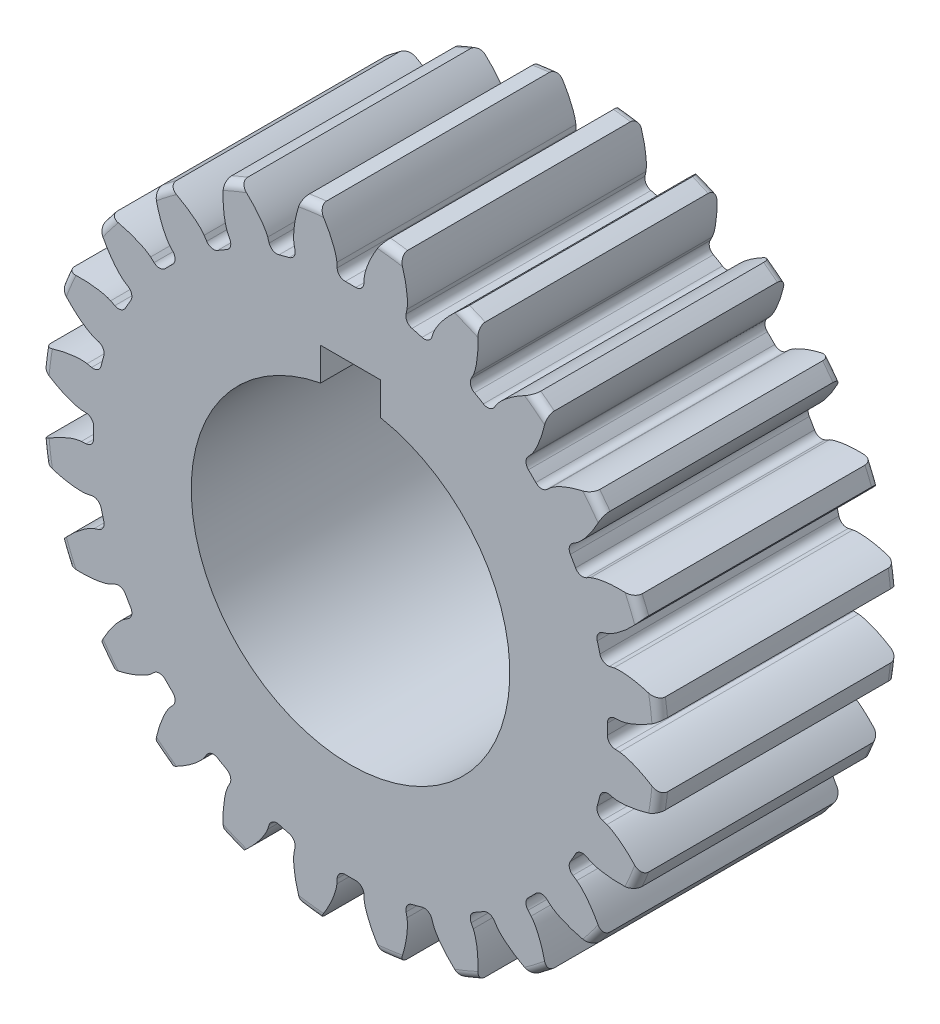
SolidWorks part; units mm, degrees
ref_plane "Front Plane" through (0, 0, 0) normal (0, 0, 1) x (1, 0, 0)
ref_plane "Top Plane" through (0, 0, 0) normal (0, 1, 0) x (1, 0, 0)
ref_plane "Right Plane" through (0, 0, 0) normal (1, 0, 0) x (0, 0, -1)
sketch "Sketch1" plane through (0, 0, 0) normal (0, 0, 1) x (1, 0, 0)
  line L0 (0, 0) -> (0, 15.24) construction
  line L1 (-4.898, 17.0227) -> (4.898, 13.4573) construction
  circle A0 centre (0, 0) radius 13.6525 construction
  circle A1 centre (0, 0) radius 16.51 construction
  circle A2 centre (0, 0) radius 15.24 construction
  circle A3 centre (0, 0) radius 14.3209 construction
  circle A4 centre (0, 0) radius 6.35 construction
  circle A5 centre (0, 0) radius 11.684 construction
  point P8 (254, 0)
  point P13 (304.8, 0)
  dimension "OD | Outside Diameter" = 33.02
  dimension "Root Diameter" = 27.305
  dimension "Gear Pitch Diameter" = 30.48
  dimension "Base Diameter" = 28.6418
  dimension "For Shaft Diameter" = 12.7
  dimension "Hub Diameter" = 23.368
  dimension "Pressure Angle" = 20
  dimension "Number of Teeth" = 609.6
  dimension "Gear Pitch | Diametral Pitch" = 508
sketch "Sketch2" plane through (0, 0, 0) normal (1, 0, 0) x (0, 0, -1)
  line L0 (-11.938, 0) -> (11.938, 0) construction
  line L1 (-11.938, 16.51) -> (11.938, 16.51) construction
  point P2 (0, 16.51)
  point P4 (-0.762, 0)
  point P6 (-0.762, 16.51)
  dimension "Overall Width" = 23.876
  dimension "Hub Width" = 11.176
  dimension "Face Width" = 12.7
sketch "Sketch3" plane through (0, 0, 0) normal (0, 0, 1) x (1, 0, 0)
  circle A0 centre (0, 0) radius 16.51
  circle A1 centre (0, 0) radius 16.51 construction
extrude "Boss-Extrude1" add sketch "Sketch3" against normal up to vertex (11.938 mm away) and the other way up to vertex (11.938 mm away) up to point (0, 0, -11.938) other way up to point (0, 0, 11.938)
sketch "Sketch5" plane through (0, 0, 0) normal (1, 0, 0) x (0, 0, -1)
  line L1 (-11.938, 16.51) -> (-0.762, 16.51)
  line L2 (-11.938, 16.51) -> (-11.938, 11.684)
  line L3 (-11.938, 11.684) -> (-0.762, 11.684)
  line L4 (-0.762, 16.51) -> (-0.762, 11.684)
  line L11 (11.938, 6.35) -> (-11.938, 6.35)
  line L12 (11.938, 6.35) -> (11.938, 0)
  line L13 (11.938, 0) -> (-11.938, 0)
  line L14 (-11.938, 6.35) -> (-11.938, 0)
  point P5 (0, 6.35)
  point P12 (0, 11.684)
revolve "Cut-Revolve1" cut sketch "Sketch5" angle 360 about L0
fillet "Fillet2" radius 0.4261 6 edges at (16.51, 0, -11.938) (6.35, 0, -11.938) (6.35, 0, 11.938) (11.684, 0, 0.762) (16.51, 0, 0.762) (11.684, 0, 11.938)
sketch "Sketch4" plane through (0, 0, 0) normal (0, 0, 1) x (1, 0, 0)
  line L0 (0, 0) -> (13.6351, 0.6898) construction
  line L2 (0, 0) -> (13.6351, -0.6898) construction
  line L4 (13.6351, 0.6898) -> (14.3026, 0.7235)
  line L5 (14.3026, -0.7235) -> (13.6351, -0.6898)
  arc A0 (13.6351, 0.6898) -> (13.6351, -0.6898) centre (0, 0) cw
  arc A3 (16.4219, 1.7037) -> (16.4219, -1.7037) centre (0, 0) cw
  circle A4 centre (0, 0) radius 16.51 construction
  spline S0 degree 4 poles (14.3026, 0.7235) (14.3061, 0.7238) (14.3158, 0.7245) (14.3342, 0.7264) (14.3642, 0.7303) (14.4023, 0.7363) (14.4514, 0.7453) (14.509, 0.7575) (14.5722, 0.7725) (14.6407, 0.7907) (14.7089, 0.8104) (14.7766, 0.8315) (14.8439, 0.8538) (14.9252, 0.8825) (15.0222, 0.919) (15.1351, 0.9648) (15.2624, 1.0204) (15.3912, 1.0811) (15.5174, 1.144) (15.644, 1.2113) (15.7659, 1.279) (15.8915, 1.3531) (16.0071, 1.4235) (16.1354, 1.5064) (16.2387, 1.5746) (16.3736, 1.6689) (16.453, 1.7259) (16.5454, 1.7941) (16.5862, 1.8252) (16.6114, 1.8444) knots 0 0 0 0 0 0.005377 0.015084 0.028532 0.04661 0.064855 0.092111 0.119476 0.146842 0.174209 0.201575 0.228941 0.256307 0.307035 0.361767 0.4165 0.471232 0.525964 0.580697 0.635429 0.690161 0.744894 0.799626 0.854358 0.909091 0.954545 1 1 1 1 1 construction
  spline S1 degree 4 poles (14.3026, 0.7235) (14.3061, 0.7238) (14.3158, 0.7245) (14.3342, 0.7264) (14.3642, 0.7303) (14.4023, 0.7363) (14.4514, 0.7453) (14.509, 0.7575) (14.5722, 0.7725) (14.6407, 0.7907) (14.7089, 0.8104) (14.7766, 0.8315) (14.8439, 0.8538) (14.9252, 0.8825) (15.0222, 0.919) (15.1351, 0.9648) (15.2624, 1.0204) (15.3912, 1.0811) (15.5174, 1.144) (15.644, 1.2113) (15.7659, 1.279) (15.8915, 1.3531) (16.0071, 1.4235) (16.1354, 1.5064) (16.2387, 1.5746) (16.3444, 1.6484) (16.3957, 1.6849) (16.4219, 1.7037) knots 0 0 0 0 0 0.005377 0.015084 0.028532 0.04661 0.064855 0.092111 0.119476 0.146842 0.174209 0.201575 0.228941 0.256307 0.307035 0.361767 0.4165 0.471232 0.525964 0.580697 0.635429 0.690161 0.744894 0.799626 0.854358 0.909091 0.909091 0.909091 0.909091 0.909091
  spline S2 degree 4 poles (14.3026, -0.7235) (14.3061, -0.7238) (14.3158, -0.7245) (14.3342, -0.7264) (14.3642, -0.7303) (14.4023, -0.7363) (14.4514, -0.7453) (14.509, -0.7575) (14.5722, -0.7725) (14.6407, -0.7907) (14.7089, -0.8104) (14.7766, -0.8315) (14.8439, -0.8538) (14.9252, -0.8825) (15.0222, -0.919) (15.1351, -0.9648) (15.2624, -1.0204) (15.3912, -1.0811) (15.5174, -1.144) (15.644, -1.2113) (15.7659, -1.279) (15.8915, -1.3531) (16.0071, -1.4235) (16.1354, -1.5064) (16.2387, -1.5746) (16.3736, -1.6689) (16.453, -1.7259) (16.5454, -1.7941) (16.5862, -1.8252) (16.6114, -1.8444) knots 0 0 0 0 0 0.005377 0.015084 0.028532 0.04661 0.064855 0.092111 0.119476 0.146842 0.174209 0.201575 0.228941 0.256307 0.307035 0.361767 0.4165 0.471232 0.525964 0.580697 0.635429 0.690161 0.744894 0.799626 0.854358 0.909091 0.954545 1 1 1 1 1 construction
  spline S3 degree 4 poles (14.3026, -0.7235) (14.3061, -0.7238) (14.3158, -0.7245) (14.3342, -0.7264) (14.3642, -0.7303) (14.4023, -0.7363) (14.4514, -0.7453) (14.509, -0.7575) (14.5722, -0.7725) (14.6407, -0.7907) (14.7089, -0.8104) (14.7766, -0.8315) (14.8439, -0.8538) (14.9252, -0.8825) (15.0222, -0.919) (15.1351, -0.9648) (15.2624, -1.0204) (15.3912, -1.0811) (15.5174, -1.144) (15.644, -1.2113) (15.7659, -1.279) (15.8915, -1.3531) (16.0071, -1.4235) (16.1354, -1.5064) (16.2387, -1.5746) (16.3444, -1.6484) (16.3957, -1.6849) (16.4219, -1.7037) knots 0 0 0 0 0 0.005377 0.015084 0.028532 0.04661 0.064855 0.092111 0.119476 0.146842 0.174209 0.201575 0.228941 0.256307 0.307035 0.361767 0.4165 0.471232 0.525964 0.580697 0.635429 0.690161 0.744894 0.799626 0.854358 0.909091 0.909091 0.909091 0.909091 0.909091
  dimension "D1" = 27.305
extrude "Cut-Extrude1" cut sketch "Sketch4" against normal through all both and the other way through all
fillet "Fillet1" radius 0.4261 2 edges at (13.6351, -0.6898, -5.588) (13.6351, 0.6898, -5.588)
pattern_circular "CirPattern1" count 24 over 360 about axis through (0, 0, 11.938) along (0, 0, -1) of "Cut-Extrude1", "Fillet1"
sketch "Sketch6" plane through (0, 0, 11.938) normal (0, 0, 1) x (1, 0, 0)
  circle A0 centre (0, 0) radius 12.9947
  dimension "D1" = 25.9895
extrude "Cut-Extrude2" cut sketch "Sketch6" against normal up to surface (11.176 mm away) up to face at (0, 0, 0.762)
sketch "Sketch7" plane through (0, 0, 0.762) normal (0, 0, 1) x (1, 0, 0)
  line L1 (1.5875, 6.8792) -> (-1.5875, 6.8792)
  line L2 (1.5875, 6.8792) -> (1.5875, 10.0542)
  line L3 (1.5875, 10.0542) -> (-1.5875, 10.0542)
  line L4 (-1.5875, 6.8792) -> (-1.5875, 10.0542)
  line L5 (1.5875, 6.8792) -> (-1.5875, 10.0542) construction
  line L6 (1.5875, 10.0542) -> (-1.5875, 6.8792) construction
  circle A0 centre (0, 0) radius 8.4667
  point P3 (0, 8.4667)
  dimension "D1" = 16.9333
  dimension "D2" = 3.175
  dimension "D3" = 3.175
extrude "Cut-Extrude3" cut sketch "Sketch7" against normal through all contours A0 L2 L3 L4 | L4 A0 L2 L1 | L2 A0 L4 L1 region at (0, -0.1695, 0.762) region at (0, 7.6486, 0.762) region at (0, 9.2349, 0.762)
equation "\"Root Diameter@Sketch1\"=\"Root Diameter\""
equation "\"OD | Outside Diameter@Sketch1\"=\"Outside Diameter\""
equation "\"D1@CirPattern1\"=\"Number of Teeth\""
equation "\"Diametral Pitch\"=20"
equation "\"Number of Teeth\"= 24"
equation "\"Pressure Angle\"=20"
equation "\"Pitch Diameter\"= \"Number of Teeth\" / \"Diametral Pitch\""
equation "\"Base Diameter\"= \"Pitch Diameter\" * cos ( \"Pressure Angle\" )"
equation "\"Outside Diameter\"= ( \"Number of Teeth\" + 2 ) / \"Diametral Pitch\""
equation "\"Dedendum\"= 1.25 / \"Diametral Pitch\""
equation "\"Root Diameter\"= \"Pitch Diameter\" - ( 2 * \"Dedendum\" )"
equation "\"Pitch Angle\"= 360deg / \"Number of Teeth\""
equation "\"Alpha\"= sqr ( \"Pitch Diameter\" ^ 2 - \"Base Diameter\" ^ 2 ) / \"Base Diameter\" * 180 / PI - \"Pressure Angle\""
equation "\"Beta\"= ( \"Pitch Angle\" / 4 - \"Alpha\" )"
equation "\"Phi\"= sqr ( ( \"Outside Diameter\" / 2 ) ^ 2 - ( \"Base Diameter\" / 2 ) ^ 2 ) / ( \"Base Diameter\" / 2 )"
equation "\"Addendum\"= 1 / \"Diametral Pitch\""
equation "\"WorkingDepth\"= 2 / \"Diametral Pitch\""
equation "\"WholeDepth\"= 2.25 / \"Diametral Pitch\""
equation "\"Clearance\"= 0.25 / \"Diametral Pitch\""
equation "\"ToothThickness\"= ( pi * 2 ) / \"Diametral Pitch\""
equation "\"CircularPitch\"= pi / \"Diametral Pitch\""
equation "\"Number of Teeth@Sketch1\"=\"Number of Teeth\""
equation "\"Gear Pitch | Diametral Pitch@Sketch1\"=\"Diametral Pitch\""
equation "\"Pressure Angle@Sketch1\"=\"Pressure Angle\""
equation "\"Gear Pitch Diameter@Sketch1\"=\"Pitch Diameter\""
equation "\"Base Diameter@Sketch1\"=\"Base Diameter\""
equation "\"Fillet\"= \"Clearance\" * cos ( \"Pressure Angle\" ) * tan ( ( 90 + \"Pressure Angle\" ) / 2 )"
equation "\"D1@Fillet1\"=\"Fillet\""
equation "\"D1@Sketch4\"=if( \"Base Diameter\">\"Root Diameter\",\"Root Diameter\",\"Base Diameter\"-.00001)"
equation "\"D1@Fillet2\"=\"Fillet\""
